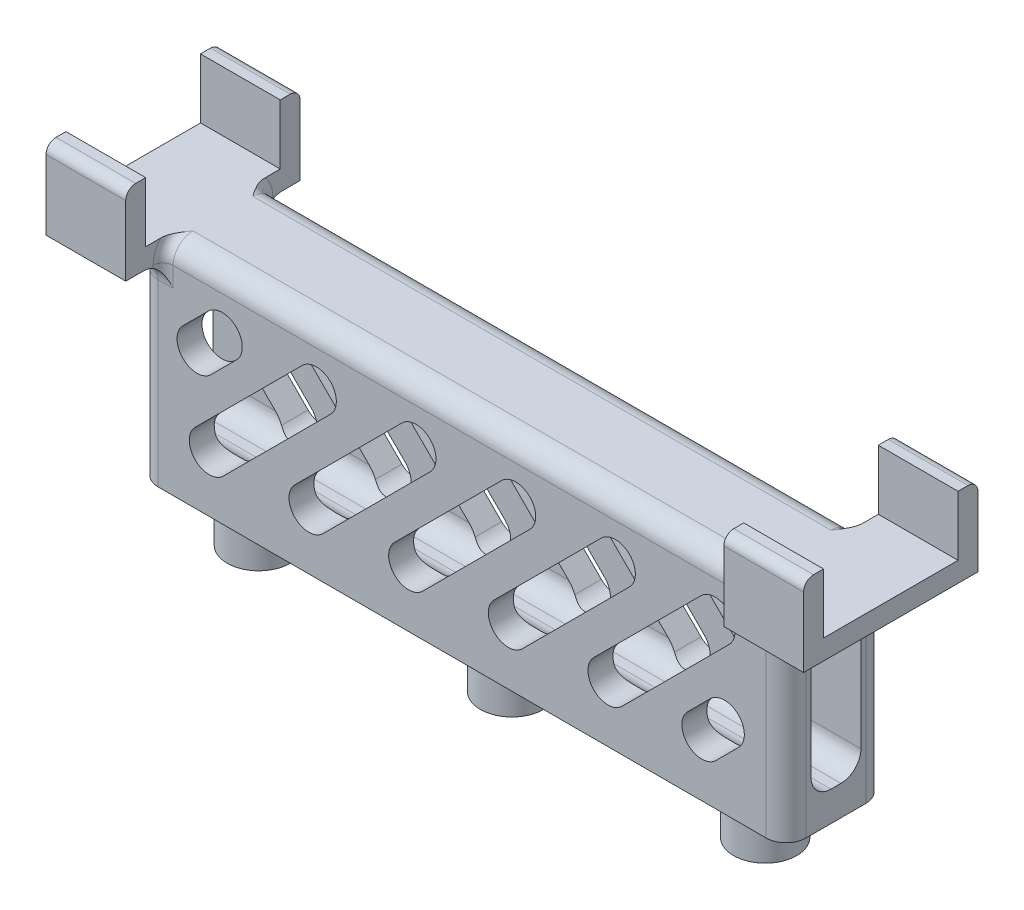
SolidWorks part; units mm, degrees
ref_plane "前视基准面" through (0, 0, 0) normal (0, 0, 1) x (1, 0, 0)
ref_plane "上视基准面" through (0, 0, 0) normal (0, 1, 0) x (1, 0, 0)
ref_plane "右视基准面" through (0, 0, 0) normal (1, 0, 0) x (0, 0, -1)
other "Configuration Table"
sketch "草图1" plane through (0, 0, 0) normal (0, 1, 0) x (1, 0, 0)
  line L0 (0, 0) -> (-26.3338, 0) construction
  line L1 (-30, 5) -> (30, 5)
  line L3 (-30, -5) -> (30, -5)
  line L5 (-30, 5) -> (30, -5) construction
  line L6 (-30, -5) -> (30, 5) construction
  line L11 (-30, -8.75) -> (-38, -8.75)
  line L12 (-30, -8.75) -> (-30, -5)
  line L13 (-30, 8.75) -> (-38, 8.75)
  line L14 (-38, -8.75) -> (-38, 8.75)
  line L15 (0, 0) -> (0, 13.1701) construction
  line L16 (30, 8.75) -> (38, 8.75)
  line L17 (38, -8.75) -> (38, 8.75)
  line L18 (30, -8.75) -> (38, -8.75)
  line L19 (30, -8.75) -> (30, -5)
  line L20 (-30, 5) -> (-30, 8.75)
  line L21 (30, 5) -> (30, 8.75)
  point P0 (0, 0)
  dimension "D1" = 60
  dimension "D2" = 8
  dimension "D3" = 17.5
  dimension "D4" = 8.75
  dimension "D5" = 10
extrude "凸台-拉伸1" add sketch "草图1" along normal blind 2
sketch "草图2" plane through (0, 2, 0) normal (0, 1, 0) x (1, 0, 0)
  line L0 (-30, 5) -> (-30, 8.75) construction
  line L1 (-38, 8.75) -> (-30, 8.75)
  line L2 (-38, 8.75) -> (-38, 6.75)
  line L3 (-38, 6.75) -> (-30, 6.75)
  line L4 (-30, 8.75) -> (-30, 6.75)
  line L5 (0, 0) -> (-14.9961, 0) construction
  line L6 (-14.9961, 0) -> (0, 0) construction
  line L7 (0, 0) -> (0, 8.3604) construction
  line L8 (-38, -6.75) -> (-30, -6.75)
  line L9 (-30, -8.75) -> (-30, -6.75)
  line L10 (-38, -8.75) -> (-30, -8.75)
  line L11 (-38, -8.75) -> (-38, -6.75)
  line L12 (38, -8.75) -> (38, -6.75)
  line L13 (38, -8.75) -> (30, -8.75)
  line L14 (30, -8.75) -> (30, -6.75)
  line L15 (38, -6.75) -> (30, -6.75)
  line L16 (38, 6.75) -> (30, 6.75)
  line L17 (30, 8.75) -> (30, 6.75)
  line L18 (38, 8.75) -> (30, 8.75)
  line L19 (38, 8.75) -> (38, 6.75)
  dimension "D1" = 2
extrude "凸台-拉伸2" add sketch "草图2" along normal blind 6
sketch "草图3" plane through (0, 0, 0) normal (0, -1, 0) x (1, 0, 0)
  line L1 (-32.5, 5) -> (32.5, 5)
  line L2 (-32.5, 5) -> (-32.5, -5)
  line L3 (-32.5, -5) -> (32.5, -5)
  line L4 (32.5, 5) -> (32.5, -5)
  line L5 (-32.5, 5) -> (32.5, -5) construction
  line L6 (-32.5, -5) -> (32.5, 5) construction
  point P0 (0, 0)
  dimension "D1" = 10
  dimension "D2" = 65
extrude "凸台-拉伸3" add sketch "草图3" along normal blind 20
sketch "草图5" plane through (32.5, 0, 0) normal (1, 0, 0) x (0, 0, -1)
  line L0 (5, 0) -> (-5, 0) construction
  line L1 (-0.5, -3) -> (0.5, -3)
  line L2 (-2.5, -5) -> (-2.5, -15)
  line L3 (-0.5, -17) -> (0.5, -17)
  line L4 (2.5, -5) -> (2.5, -15)
  line L5 (-2.5, -3) -> (2.5, -17) construction
  line L6 (-2.5, -17) -> (2.5, -3) construction
  line L7 (5, -20) -> (-5, -20) construction
  line L8 (5, -20) -> (5, 0) construction
  line L9 (-5, -20) -> (-5, 0) construction
  arc A0 (-2.5, -15) -> (-0.5, -17) centre (-0.5, -15) ccw
  arc A1 (0.5, -17) -> (2.5, -15) centre (0.5, -15) ccw
  arc A2 (0.5, -3) -> (2.5, -5) centre (0.5, -5) cw
  arc A3 (-0.5, -3) -> (-2.5, -5) centre (-0.5, -5) ccw
  point P0 (0, -10)
  dimension "D5" = 2
  dimension "D1" = 3
  dimension "D2" = 3
  dimension "D3" = 2.5
  dimension "D4" = 2.5
extrude "切除-拉伸2" cut sketch "草图5" against normal blind 100
sketch "草图6" plane through (0, -20, 0) normal (0, -1, 0) x (1, 0, 0)
  circle A0 centre (0, 0) radius 3.17
  circle A1 centre (25.4, 0) radius 3.17
  circle A2 centre (-25.4, 0) radius 3.17
  dimension "D1" = 25.4
  dimension "D2" = 25.4
extrude "凸台-拉伸4" add sketch "草图6" along normal blind 5
sketch "草图7" plane through (0, 0, -5) normal (0, 0, -1) x (-1, 0, 0)
  line L0 (-26.5942, -6.1716) -> (-24.0486, -3.626) construction
  line L5 (-28.0084, -4.7574) -> (-25.4628, -2.2118)
  line L6 (-25.18, -7.5858) -> (-22.6344, -5.0402)
  line L7 (0, -9) -> (0, 7.5741) construction
  line L8 (24.0447, -14.374) -> (26.9393, -11.4794) construction
  line L11 (4.626, -14.374) -> (15.374, -3.626) construction
  line L14 (3.2118, -12.9598) -> (13.9598, -2.2118)
  line L17 (6.0402, -15.7882) -> (16.7882, -5.0402)
  line L20 (-5.374, -14.374) -> (5.374, -3.626) construction
  line L21 (-6.7882, -12.9598) -> (3.9598, -2.2118)
  line L22 (-3.9598, -15.7882) -> (6.7882, -5.0402)
  line L23 (14.626, -14.374) -> (25.374, -3.626) construction
  line L24 (13.2118, -12.9598) -> (23.9598, -2.2118)
  line L25 (16.0402, -15.7882) -> (26.7882, -5.0402)
  line L26 (-15.374, -14.374) -> (-4.626, -3.626) construction
  line L27 (-16.7882, -12.9598) -> (-6.0402, -2.2118)
  line L28 (-13.9598, -15.7882) -> (-3.2118, -5.0402)
  line L29 (-25.374, -14.374) -> (-14.626, -3.626) construction
  line L30 (-26.7882, -12.9598) -> (-16.0402, -2.2118)
  line L31 (-23.9598, -15.7882) -> (-13.2118, -5.0402)
  line L32 (-25.3214, -4.8988) -> (-25.3214, 5.9106) construction
  line L33 (22.6304, -12.9598) -> (25.5251, -10.0652)
  line L34 (25.4589, -15.7882) -> (28.3535, -12.8936)
  line L35 (-30, 2) -> (30, 2) construction
  arc A8 (-6.7882, -12.9598) -> (-3.9598, -15.7882) centre (-5.374, -14.374) ccw
  arc A9 (6.7882, -5.0402) -> (3.9598, -2.2118) centre (5.374, -3.626) ccw
  arc A10 (3.2118, -12.9598) -> (6.0402, -15.7882) centre (4.626, -14.374) ccw
  arc A11 (16.7882, -5.0402) -> (13.9598, -2.2118) centre (15.374, -3.626) ccw
  arc A12 (13.2118, -12.9598) -> (16.0402, -15.7882) centre (14.626, -14.374) ccw
  arc A13 (26.7882, -5.0402) -> (23.9598, -2.2118) centre (25.374, -3.626) ccw
  arc A14 (-16.7882, -12.9598) -> (-13.9598, -15.7882) centre (-15.374, -14.374) ccw
  arc A15 (-3.2118, -5.0402) -> (-6.0402, -2.2118) centre (-4.626, -3.626) ccw
  arc A16 (-26.7882, -12.9598) -> (-23.9598, -15.7882) centre (-25.374, -14.374) ccw
  arc A17 (-13.2118, -5.0402) -> (-16.0402, -2.2118) centre (-14.626, -3.626) ccw
  arc A18 (-28.0084, -4.7574) -> (-25.18, -7.5858) centre (-26.5942, -6.1716) ccw
  arc A19 (-22.6344, -5.0402) -> (-25.4628, -2.2118) centre (-24.0486, -3.626) ccw
  arc A20 (22.6304, -12.9598) -> (25.4589, -15.7882) centre (24.0447, -14.374) ccw
  arc A21 (28.3535, -12.8936) -> (25.5251, -10.0652) centre (26.9393, -11.4794) ccw
  point P0 (0, -9)
  point P3 (-25.3214, -4.8988)
  point P8 (0, 0)
  point P9 (0, 0)
  point P10 (0, 0)
  point P11 (0, 0)
  point P12 (0, 0)
  point P13 (0, 0)
  point P17 (10, -9)
  point P23 (-26.7882, -6.368)
  point P25 (20, -9)
  point P32 (-10, -9)
  point P36 (0, -9)
  point P47 (-20, -9)
  point P57 (25.492, -12.9267)
  point P62 (0, 0)
  point P63 (0, 0)
  point P64 (0, 0)
  point P65 (0, 0)
  point P66 (0, 0)
  point P67 (0, 0)
  dimension "D2" = 45
  dimension "D3" = 45
  dimension "D4" = 7.6
  dimension "D5" = 2
  dimension "D6" = 1.8
  dimension "D7" = 2
  dimension "D8" = 6.7184
  dimension "D9" = 10
  dimension "D10" = 10
  dimension "D11" = 10
  dimension "D12" = 10
  dimension "D13" = 3.0711
  dimension "D14" = 2.6628
  dimension "D15" = 2.66
  dimension "D16" = 4
  dimension "D17" = 4
  dimension "D18" = 11
extrude "切除-拉伸3" cut sketch "草图7" against normal blind 5
sketch "草图9" plane through (0, 0, 5) normal (0, 0, 1) x (1, 0, 0)
  line L0 (0, -9) -> (0, 12.7484) construction
  line L1 (-5.374, -14.374) -> (5.374, -3.626) construction
  line L2 (-6.7882, -12.9598) -> (3.9598, -2.2118)
  line L3 (-3.9598, -15.7882) -> (6.7882, -5.0402)
  line L4 (-30, 2) -> (30, 2) construction
  line L5 (6.0402, -15.7882) -> (16.7882, -5.0402)
  line L6 (3.2118, -12.9598) -> (13.9598, -2.2118)
  line L7 (4.626, -14.374) -> (15.374, -3.626) construction
  line L8 (16.0402, -15.7882) -> (26.7882, -5.0402)
  line L9 (13.2118, -12.9598) -> (23.9598, -2.2118)
  line L10 (14.626, -14.374) -> (25.374, -3.626) construction
  line L11 (-15.374, -14.374) -> (-4.626, -3.626) construction
  line L12 (-16.7882, -12.9598) -> (-6.0402, -2.2118)
  line L13 (-13.9598, -15.7882) -> (-3.2118, -5.0402)
  line L14 (-25.374, -14.374) -> (-14.626, -3.626) construction
  line L15 (-26.7882, -12.9598) -> (-16.0402, -2.2118)
  line L16 (-23.9598, -15.7882) -> (-13.2118, -5.0402)
  line L17 (-26.6042, -6.1716) -> (-24.0586, -3.626) construction
  line L18 (-28.0184, -4.7574) -> (-25.4728, -2.2118)
  line L19 (-25.19, -7.5858) -> (-22.6444, -5.0402)
  line L20 (24.0447, -14.374) -> (26.3074, -12.1113) construction
  line L21 (22.6304, -12.9598) -> (24.8932, -10.6971)
  line L22 (25.4589, -15.7882) -> (27.7216, -13.5255)
  arc A0 (-6.7882, -12.9598) -> (-3.9598, -15.7882) centre (-5.374, -14.374) ccw
  arc A1 (6.7882, -5.0402) -> (3.9598, -2.2118) centre (5.374, -3.626) ccw
  arc A2 (3.2118, -12.9598) -> (6.0402, -15.7882) centre (4.626, -14.374) ccw
  arc A3 (16.7882, -5.0402) -> (13.9598, -2.2118) centre (15.374, -3.626) ccw
  arc A4 (13.2118, -12.9598) -> (16.0402, -15.7882) centre (14.626, -14.374) ccw
  arc A5 (26.7882, -5.0402) -> (23.9598, -2.2118) centre (25.374, -3.626) ccw
  arc A6 (-16.7882, -12.9598) -> (-13.9598, -15.7882) centre (-15.374, -14.374) ccw
  arc A7 (-3.2118, -5.0402) -> (-6.0402, -2.2118) centre (-4.626, -3.626) ccw
  arc A8 (-26.7882, -12.9598) -> (-23.9598, -15.7882) centre (-25.374, -14.374) ccw
  arc A9 (-13.2118, -5.0402) -> (-16.0402, -2.2118) centre (-14.626, -3.626) ccw
  arc A10 (-28.0184, -4.7574) -> (-25.19, -7.5858) centre (-26.6042, -6.1716) ccw
  arc A11 (-22.6444, -5.0402) -> (-25.4728, -2.2118) centre (-24.0586, -3.626) ccw
  arc A12 (22.6304, -12.9598) -> (25.4589, -15.7882) centre (24.0447, -14.374) ccw
  arc A13 (27.7216, -13.5255) -> (24.8932, -10.6971) centre (26.3074, -12.1113) ccw
  point P5 (0, -9)
  point P15 (10, -9)
  point P22 (20, -9)
  point P29 (-10, -9)
  point P36 (-20, -9)
  point P42 (-25.3314, -4.8988)
  point P47 (0, 0)
  point P50 (25.176, -13.2426)
  point P55 (0, 0)
  point P58 (12.3389, -8.1409)
  dimension "D1" = 11
  dimension "D2" = 4
  dimension "D3" = 7.6
  dimension "D4" = 45
  dimension "D7" = 45
  dimension "D9" = 1.8
  dimension "D10" = 2.66
  dimension "D11" = 2
  dimension "D12" = 1.6
  dimension "D5" = 3
  dimension "D6" = 3
extrude "切除-拉伸4" cut sketch "草图9" against normal blind 5
fillet "圆角9" radius 2 2 edges at (0, 2, -5) (0, 2, 5)
fillet "圆角10" radius 2 4 edges at (32.5, -10, -5) (32.5, -10, 5) (-32.5, -10, -5) (-32.5, -10, 5)
fillet "圆角11" radius 2 10 edges at (30.25, 0, -5) (31.9142, 0, -4.4142) (30.25, 0, 5) (31.9142, 0, 4.4142) (-30.25, 0, 5) (-31.9142, 0, 4.4142) (-30.25, 0, -5) (-31.9142, 0, -4.4142) (32.5, 0, 0) (-32.5, 0, 0)
fillet "圆角12" radius 1 4 edges at (-34, 8, -8.75) (34, 8, -8.75) (34, 8, 8.75) (-34, 8, 8.75)
fillet "圆角13" radius 1 8 edges at (-30, -1, -5) (30, -1, -5) (30, -1, 5) (-30, -1, 5) (-30, 1.4142, -4.4142) (30, 1.4142, -4.4142) (30, 1.4142, 4.4142) (-30, 1.4142, 4.4142)
